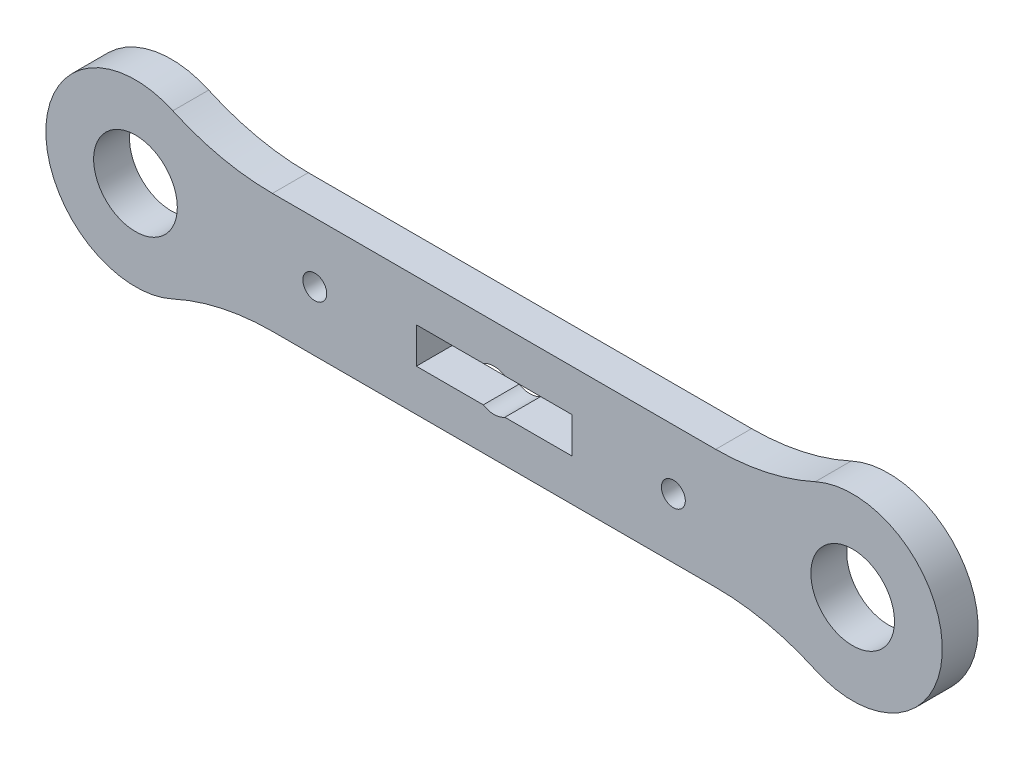
SolidWorks part; units mm, degrees
ref_plane "Plano frontal" through (0, 0, 0) normal (0, 0, 1) x (1, 0, 0)
ref_plane "Plano superior" through (0, 0, 0) normal (0, 1, 0) x (1, 0, 0)
ref_plane "Plano direito" through (0, 0, 0) normal (1, 0, 0) x (0, 0, -1)
sketch "Esboço1" plane through (0, 0, 0) normal (0, 0, 1) x (1, 0, 0)
  line L0 (5.5902, -5) -> (54.4098, -5)
  line L1 (0, 0) -> (60, 0) construction
  line L2 (5.5902, 5) -> (54.4098, 5)
  line L3 (0, 5) -> (80, 5) construction
  line L4 (0, -5) -> (80, -5) construction
  line L5 (30, 5) -> (30, -5) construction
  line L6 (30.9014, 1.5) -> (36.5, 1.5)
  line L7 (0, 0) -> (80, 0) construction
  line L8 (23.5, 1.5) -> (29.0986, 1.5)
  line L9 (23.5, 1.5) -> (23.5, -1.5)
  line L10 (23.5, -1.5) -> (29.0986, -1.5)
  line L11 (36.5, 1.5) -> (36.5, -1.5)
  line L12 (23.5, 1.5) -> (36.5, -1.5) construction
  line L13 (23.5, -1.5) -> (36.5, 1.5) construction
  line L14 (30.9014, -1.5) -> (36.5, -1.5)
  circle A0 centre (45, 0) radius 1
  circle A1 centre (15, 0) radius 1
  arc A2 (29.0986, -1.5) -> (30.9014, -1.5) centre (30, 0) ccw
  arc A3 (5.5902, 5) -> (5.5902, -5) centre (0, 0) ccw
  arc A4 (30.9014, 1.5) -> (29.0986, 1.5) centre (30, 0) ccw
  circle A13 centre (0, 0) radius 3.5
  arc A22 (54.4098, 5) -> (54.4098, -5) centre (60, 0) cw
  circle A25 centre (60, 0) radius 3.5
  point P14 (30, 0)
  point P15 (30, 0)
  point P32 (0, 0)
  dimension "D1" = 3
  dimension "D3" = 2
  dimension "D4" = 15
  dimension "D6" = 7
  dimension "D8" = 15
  dimension "D9" = 13
  dimension "D10" = 3.5
  dimension "D2" = 5
  dimension "D5" = 5
  dimension "D7" = 30
extrude "Ressalto-extrusão1" add sketch "Esboço1" along normal blind 3 contours A22 L2 A3 L0 A1 region at (-6.7351, 0, 0)
fillet "Filete1" radius 20 4 edges at (5.5902, -5, 1.5) (54.4098, -5, 1.5) (54.4098, 5, 1.5) (5.5902, 5, 1.5)
